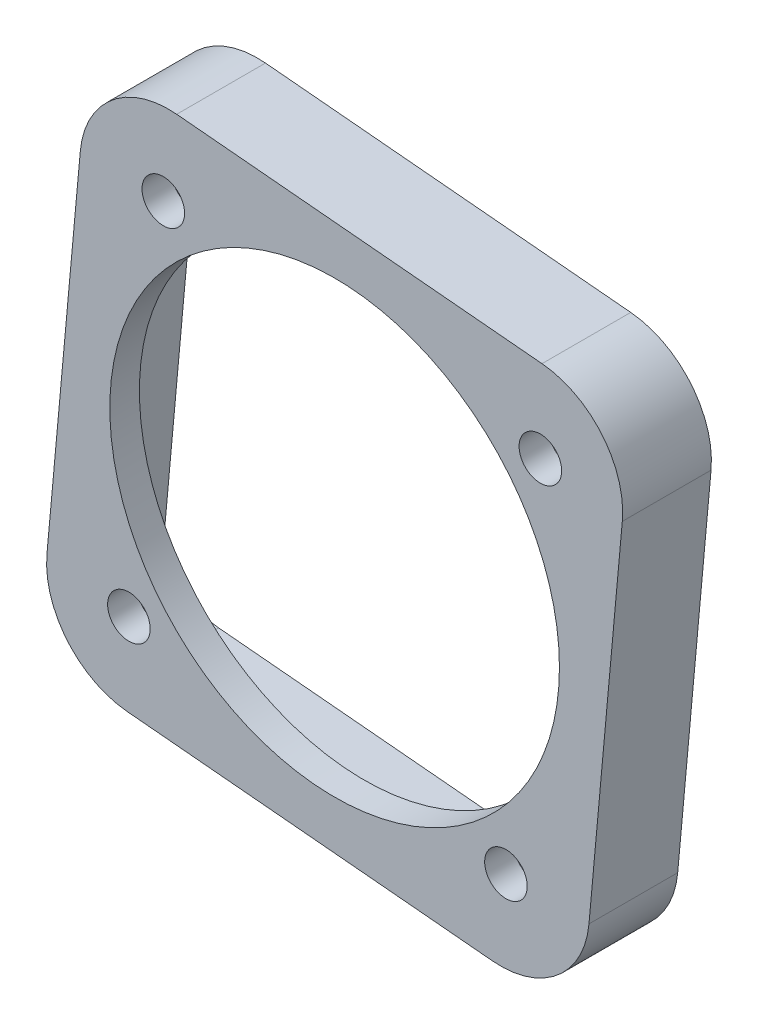
SolidWorks part; units mm, degrees
material "Custom Plastic"
ref_plane "X-Y Datum" through (0, 0, 0) normal (0, 0, 1) x (1, 0, 0)
ref_plane "X-Z Datum" through (0, 0, 0) normal (0, 1, 0) x (1, 0, 0)
ref_plane "Y-Z Datum" through (0, 0, 0) normal (1, 0, 0) x (0, 0, -1)
sketch "Sketch2" plane through (0, 0, -2122.6666) normal (0, 0, 1) x (1, 0, 0)
  line L0 (127.4318, 119.7896) -> (130.2492, 150.6613) construction
  line L1 (162.3759, 112.0819) -> (131.5042, 114.8992) construction
  line L2 (167.5614, 119.388) -> (167.2662, 116.1543) construction
  line L3 (167.7207, 121.1336) -> (167.5614, 119.388) construction
  line L4 (167.7207, 121.1336) -> (167.7479, 121.4323) construction
  line L5 (167.9297, 123.4241) -> (167.957, 123.7228) construction
  line L6 (168.2387, 126.81) -> (167.957, 123.7228) construction
  line L7 (170.0836, 147.026) -> (168.2387, 126.81) construction
  line L8 (135.1395, 154.7337) -> (166.0112, 151.9163) construction
  line L9 (127.4318, 119.7896) -> (130.2492, 150.6613) construction
  line L10 (162.3759, 112.0819) -> (131.5042, 114.8992) construction
  line L11 (167.5614, 119.388) -> (167.2662, 116.1543) construction
  line L12 (167.7207, 121.1336) -> (167.5614, 119.388) construction
  line L13 (167.7207, 121.1336) -> (167.7479, 121.4323) construction
  line L14 (167.9297, 123.4241) -> (167.957, 123.7228) construction
  line L15 (168.2387, 126.81) -> (167.957, 123.7228) construction
  line L16 (170.0836, 147.026) -> (168.2387, 126.81) construction
  line L17 (135.1395, 154.7337) -> (166.0112, 151.9163) construction
  line L18 (167.9297, 123.4241) -> (167.7479, 121.4323) construction
  line L19 (168.7366, 126.7645) -> (168.4549, 123.6774)
  line L20 (168.4276, 123.3786) -> (168.4549, 123.6774)
  line L21 (168.4276, 123.3786) -> (168.2459, 121.3869)
  line L22 (168.2186, 121.0881) -> (168.2459, 121.3869)
  line L23 (168.2186, 121.0881) -> (168.0593, 119.3426)
  line L24 (168.0593, 119.3426) -> (167.7642, 116.1088)
  line L25 (162.3305, 111.5839) -> (131.4587, 114.4013)
  line L26 (126.9339, 119.835) -> (129.7512, 150.7067)
  line L27 (135.1849, 155.2316) -> (166.0567, 152.4143)
  line L28 (170.5815, 146.9805) -> (168.7366, 126.7645)
  line L29 (135.4122, 157.7213) -> (166.2839, 154.9039)
  line L30 (173.0712, 146.7533) -> (171.2263, 126.5373)
  line L31 (171.2263, 126.5373) -> (170.9445, 123.4502)
  line L32 (170.9173, 123.1514) -> (170.9445, 123.4502)
  line L33 (170.9173, 123.1514) -> (170.7355, 121.1597)
  line L34 (170.7082, 120.8609) -> (170.7355, 121.1597)
  line L35 (170.7082, 120.8609) -> (170.5489, 119.1154)
  line L36 (170.5489, 119.1154) -> (170.2538, 115.8816)
  line L37 (162.1033, 109.0943) -> (131.2315, 111.9116)
  line L38 (124.4442, 120.0622) -> (127.2616, 150.9339)
  line L39 (127.1828, 119.8123) -> (130.0002, 150.684)
  line L40 (162.3532, 111.8329) -> (131.4815, 114.6503)
  line L41 (167.8103, 119.3653) -> (167.5152, 116.1315)
  line L42 (167.9696, 121.1108) -> (167.8103, 119.3653)
  line L43 (167.9696, 121.1108) -> (167.9969, 121.4096)
  line L44 (168.1787, 123.4013) -> (167.9969, 121.4096)
  line L45 (168.1787, 123.4013) -> (168.2059, 123.7001)
  line L46 (168.4877, 126.7873) -> (168.2059, 123.7001)
  line L47 (170.3326, 147.0033) -> (168.4877, 126.7873)
  line L48 (135.1622, 154.9827) -> (166.0339, 152.1653)
  arc A0 (164.1041, 148.0737) -> (168.1871, 147.7011) centre (166.1456, 147.8874) ccw construction
  arc A1 (168.1871, 147.7011) -> (164.1041, 148.0737) centre (166.1456, 147.8874) ccw construction
  arc A2 (161.1958, 116.2062) -> (165.2789, 115.8336) centre (163.2374, 116.0199) ccw construction
  arc A3 (165.2789, 115.8336) -> (161.1958, 116.2062) centre (163.2374, 116.0199) ccw construction
  arc A4 (129.3283, 119.1144) -> (133.4113, 118.7418) centre (131.3698, 118.9281) ccw construction
  arc A5 (133.4113, 118.7418) -> (129.3283, 119.1144) centre (131.3698, 118.9281) ccw construction
  arc A6 (132.2365, 150.982) -> (136.3196, 150.6094) centre (134.278, 150.7957) ccw construction
  arc A7 (136.3196, 150.6094) -> (132.2365, 150.982) centre (134.278, 150.7957) ccw construction
  arc A8 (127.4318, 119.7896) -> (131.5042, 114.8992) centre (131.9132, 119.3806) ccw construction
  arc A9 (162.3759, 112.0819) -> (167.2662, 116.1543) centre (162.7849, 116.5632) ccw construction
  arc A10 (170.0836, 147.026) -> (166.0112, 151.9163) centre (165.6022, 147.4349) ccw construction
  arc A11 (135.1395, 154.7337) -> (130.2492, 150.6613) centre (134.7305, 150.2523) ccw construction
  arc A12 (164.1041, 148.0737) -> (168.1871, 147.7011) centre (166.1456, 147.8874) ccw construction
  arc A13 (168.1871, 147.7011) -> (164.1041, 148.0737) centre (166.1456, 147.8874) ccw construction
  arc A14 (161.1958, 116.2062) -> (165.2789, 115.8336) centre (163.2374, 116.0199) ccw construction
  arc A15 (165.2789, 115.8336) -> (161.1958, 116.2062) centre (163.2374, 116.0199) ccw construction
  arc A16 (129.3283, 119.1144) -> (133.4113, 118.7418) centre (131.3698, 118.9281) ccw construction
  arc A17 (133.4113, 118.7418) -> (129.3283, 119.1144) centre (131.3698, 118.9281) ccw construction
  arc A18 (132.2365, 150.982) -> (136.3196, 150.6094) centre (134.278, 150.7957) ccw construction
  arc A19 (136.3196, 150.6094) -> (132.2365, 150.982) centre (134.278, 150.7957) ccw construction
  arc A20 (127.4318, 119.7896) -> (131.5042, 114.8992) centre (131.9132, 119.3806) ccw construction
  arc A21 (162.3759, 112.0819) -> (167.2662, 116.1543) centre (162.7849, 116.5632) ccw construction
  arc A22 (170.0836, 147.026) -> (166.0112, 151.9163) centre (165.6022, 147.4349) ccw construction
  arc A23 (135.1395, 154.7337) -> (130.2492, 150.6613) centre (134.7305, 150.2523) ccw construction
  arc A24 (162.3305, 111.5839) -> (167.7642, 116.1088) centre (162.7849, 116.5632) ccw
  arc A25 (126.9339, 119.835) -> (131.4587, 114.4013) centre (131.9132, 119.3806) ccw
  arc A26 (135.1849, 155.2316) -> (129.7512, 150.7067) centre (134.7305, 150.2523) ccw
  arc A27 (170.5815, 146.9805) -> (166.0567, 152.4143) centre (165.6022, 147.4349) ccw
  arc A28 (173.0712, 146.7533) -> (166.2839, 154.9039) centre (165.6022, 147.4349) ccw
  arc A29 (162.1033, 109.0943) -> (170.2538, 115.8816) centre (162.7849, 116.5632) ccw
  arc A30 (124.4442, 120.0622) -> (131.2315, 111.9116) centre (131.9132, 119.3806) ccw
  arc A31 (135.4122, 157.7213) -> (127.2616, 150.9339) centre (134.7305, 150.2523) ccw
  arc A32 (129.7838, 134.4027) -> (129.7588, 133.6103) centre (148.7577, 133.4078) ccw construction
  arc A33 (129.7588, 133.6103) -> (131.7102, 125.0183) centre (148.7577, 133.4078) ccw construction
  arc A34 (137.0704, 148.388) -> (131.5696, 141.5053) centre (148.7577, 133.4078) ccw construction
  arc A35 (129.7838, 134.4027) -> (129.7588, 133.6103) centre (148.7577, 133.4078) ccw
  arc A36 (129.7588, 133.6103) -> (131.7102, 125.0183) centre (148.7577, 133.4078) ccw
  arc A37 (137.0704, 148.388) -> (131.5696, 141.5053) centre (148.7577, 133.4078) ccw
  circle A38 centre (148.7577, 133.4078) radius 19
  arc A39 (135.1622, 154.9827) -> (130.0002, 150.684) centre (134.7305, 150.2523) ccw
  arc A40 (127.1828, 119.8123) -> (131.4815, 114.6503) centre (131.9132, 119.3806) ccw
  arc A41 (162.3532, 111.8329) -> (167.5152, 116.1315) centre (162.7849, 116.5632) ccw
  arc A42 (170.3326, 147.0033) -> (166.0339, 152.1653) centre (165.6022, 147.4349) ccw
  dimension "D1" = 0.5
  dimension "D2" = 2.5
  dimension "D3" = 0.25
extrude "Boss-Extrude2" add sketch "Sketch2" along normal blind 2.5 contours L47 A42 L48 A39 L39 A40 L40 A41 L41 L42 L43 L44 L45 L46 A38 A37 A36 A35 | L28 A27 L27 A26 L26 A25 L25 A24 L24 L23 L22 L21 L20 L19 A42 L47 L46 L45 L44 L43 L42 L41 A41 L40 A40 L39 A39 L48 | L29 A31 L38 A30 L37 A29 L36 L35 L34 L33 L32 L31 L30 A28 A27 L28 L19 L20 L21 L22 L23 L24 A24 L25 A25 L26 A26 L27 region at (168.5342, 125.2266, -2122.6666) region at (150.7854, 155.6269, -2122.6666) region at (129.1998, 135.1926, -2122.6666)
sketch "Sketch4" plane through (0, 0, -2122.6666) normal (0, 0, -1) x (-1, 0, 0)
  line L0 (-135.1849, 155.2316) -> (-166.0567, 152.4143)
  line L1 (-170.5815, 146.9805) -> (-167.7642, 116.1088)
  line L2 (-162.3305, 111.5839) -> (-131.4587, 114.4013)
  line L3 (-126.9339, 119.835) -> (-129.7512, 150.7067)
  line L4 (-135.4122, 157.7213) -> (-166.2839, 154.9039)
  line L5 (-173.0712, 146.7533) -> (-170.2538, 115.8816)
  line L6 (-162.1033, 109.0943) -> (-131.2315, 111.9116)
  line L7 (-124.4442, 120.0622) -> (-127.2616, 150.9339)
  line L8 (-135.4122, 157.7213) -> (-166.2839, 154.9039)
  line L9 (-173.0712, 146.7533) -> (-170.2538, 115.8816)
  line L10 (-162.1033, 109.0943) -> (-131.2315, 111.9116)
  line L11 (-124.4442, 120.0622) -> (-127.2616, 150.9339)
  arc A0 (-166.0567, 152.4143) -> (-170.5815, 146.9805) centre (-165.6022, 147.4349) ccw
  arc A1 (-167.7642, 116.1088) -> (-162.3305, 111.5839) centre (-162.7849, 116.5632) ccw
  arc A2 (-131.4587, 114.4013) -> (-126.9339, 119.835) centre (-131.9132, 119.3806) ccw
  arc A3 (-129.7512, 150.7067) -> (-135.1849, 155.2316) centre (-134.7305, 150.2523) ccw
  arc A4 (-166.2839, 154.9039) -> (-173.0712, 146.7533) centre (-165.6022, 147.4349) ccw
  arc A5 (-170.2538, 115.8816) -> (-162.1033, 109.0943) centre (-162.7849, 116.5632) ccw
  arc A6 (-131.2315, 111.9116) -> (-124.4442, 120.0622) centre (-131.9132, 119.3806) ccw
  arc A7 (-127.2616, 150.9339) -> (-135.4122, 157.7213) centre (-134.7305, 150.2523) ccw
  arc A8 (-166.2839, 154.9039) -> (-173.0712, 146.7533) centre (-165.6022, 147.4349) ccw
  arc A9 (-170.2538, 115.8816) -> (-162.1033, 109.0943) centre (-162.7849, 116.5632) ccw
  arc A10 (-131.2315, 111.9116) -> (-124.4442, 120.0622) centre (-131.9132, 119.3806) ccw
  arc A11 (-127.2616, 150.9339) -> (-135.4122, 157.7213) centre (-134.7305, 150.2523) ccw
  dimension "D1" = 0
  dimension "D2" = 2.5
extrude "Boss-Extrude3" add sketch "Sketch4" along normal blind 5
hole_wizard "M3 Clearance Hole1" positions "Sketch9" profile "Sketch8" hole size "M3" standard "ANSI Metric" end condition up to next
sketch "Sketch9" plane through (0, 0, -2120.1666) normal (0, 0, 1) x (1, 0, 0)
  point P0 (134.278, 150.7957)
  point P3 (131.3698, 118.9281)
  point P6 (163.2374, 116.0199)
  point P9 (166.1456, 147.8874)
sketch "Sketch8" plane through (134.278, 150.7957, -2120.1666) normal (1, 0, 0) x (0, -1, 0)
  line L0 (0, 0) -> (0, 2.5)
  line L1 (0, 2.5) -> (1.8, 2.5)
  line L2 (1.8, 2.5) -> (1.8, 0)
  line L5 (1.8, 0) -> (0, 0)
  line L11 (0, -6.35) -> (0, 107.95) construction
  dimension "Thru Hole Dia." = 3.6
  dimension "Thru Hole Depth" = 2.5
